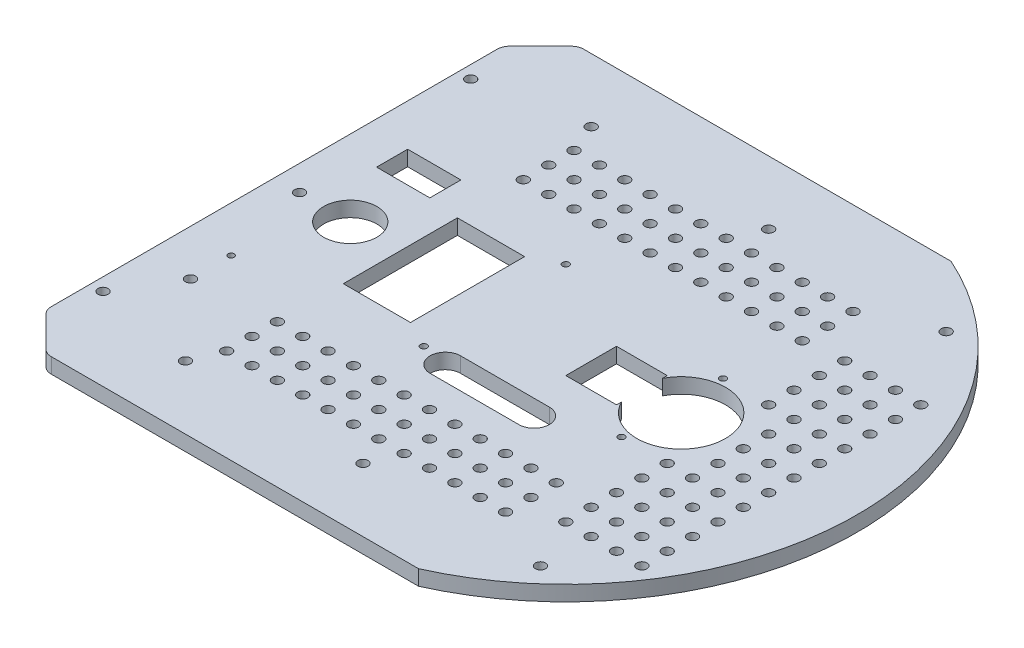
SolidWorks part; units mm, degrees
ref_plane "Front Plane" through (0, 0, 0) normal (0, 0, 1) x (1, 0, 0)
ref_plane "Top Plane" through (0, 0, 0) normal (0, 1, 0) x (1, 0, 0)
ref_plane "Right Plane" through (0, 0, 0) normal (1, 0, 0) x (0, 0, -1)
sketch "Sketch1" plane through (0, 0, 0) normal (0, 1, 0) x (1, 0, 0)
  line L0 (0, 80) -> (0, -80) construction
  line L1 (-46.9042, -105) -> (46.9042, -105)
  line L2 (-46.9042, 105) -> (46.9042, 105)
  line L7 (-70, 0) -> (70, 0) construction
  line L8 (-70, 80) -> (70, 80) construction
  line L9 (-70, 80) -> (-70, -80) construction
  line L10 (-70, -80) -> (70, -80) construction
  line L11 (70, 80) -> (70, -80) construction
  circle A0 centre (-70, 80) radius 2
  circle A1 centre (70, 80) radius 2
  circle A2 centre (70, -80) radius 2
  circle A3 centre (-70, -80) radius 2
  circle A4 centre (0, 80) radius 2
  circle A5 centre (70, 0) radius 2
  circle A6 centre (0, -80) radius 2
  arc A8 (-46.9042, 105) -> (-46.9042, -105) centre (0, 0) ccw
  arc A9 (46.9042, -105) -> (46.9042, 105) centre (0, 0) ccw
  point P0 (0, 0)
  point P13 (0, 0)
  dimension "D1" = 105
  dimension "D8" = 230
  dimension "D5" = 4
  dimension "D2" = 140
  dimension "D3" = 160
  dimension "D4" = 105
extrude "Boss-Extrude1" add sketch "Sketch1" along normal blind 6
sketch "Sketch2" plane through (0, 6, 0) normal (0, 1, 0) x (1, 0, 0)
  line L0 (0, 105) -> (0, -105) construction
  line L1 (46.9042, 105) -> (-46.9042, 105) construction
  line L2 (-46.9042, -105) -> (46.9042, -105) construction
  line L3 (-115, 0) -> (115, 0) construction
  line L4 (-17.5, -30) -> (17.5, -30) construction
  line L5 (-65.25, -22.5) -> (-38.75, -22.5)
  line L6 (-65.25, -22.5) -> (-65.25, 22.5)
  line L7 (-65.25, 22.5) -> (-38.75, 22.5)
  line L8 (-38.75, -22.5) -> (-38.75, 22.5)
  line L9 (-65.25, -22.5) -> (-38.75, 22.5) construction
  line L10 (-65.25, 22.5) -> (-38.75, -22.5) construction
  line L11 (-17.5, -24) -> (17.5, -24)
  line L12 (-17.5, -36) -> (17.5, -36)
  arc A0 (-46.9042, 105) -> (-46.9042, -105) centre (0, 0) ccw construction
  arc A1 (46.9042, -105) -> (46.9042, 105) centre (0, 0) ccw construction
  circle A2 centre (0, 0) radius 35 construction
  circle A3 centre (-28, 28) radius 1.3
  circle A4 centre (-28, -28) radius 1.3
  circle A5 centre (42, 20) radius 1.3
  circle A6 centre (42, -20) radius 1.3
  circle A7 centre (-85, 0) radius 10.5
  circle A8 centre (-97, -35) radius 1.2
  circle A10 centre (-97, -51) radius 2
  circle A12 centre (-105, 0) radius 2
  circle A13 centre (60, 50) radius 2
  circle A14 centre (70, 50) radius 2
  circle A15 centre (80, 50) radius 2
  circle A16 centre (90, 50) radius 2
  circle A17 centre (70, 40) radius 2
  circle A18 centre (80, 40) radius 2
  circle A19 centre (90, 40) radius 2
  circle A20 centre (70, 30) radius 2
  circle A21 centre (80, 30) radius 2
  circle A22 centre (90, 30) radius 2
  circle A23 centre (70, 20) radius 2
  circle A24 centre (80, 20) radius 2
  circle A25 centre (90, 20) radius 2
  circle A26 centre (70, 10) radius 2
  circle A27 centre (80, 10) radius 2
  circle A28 centre (90, 10) radius 2
  circle A29 centre (70, 0) radius 2
  circle A30 centre (80, 0) radius 2
  circle A31 centre (90, 0) radius 2
  circle A32 centre (70, -10) radius 2
  circle A33 centre (80, -10) radius 2
  circle A34 centre (90, -10) radius 2
  circle A35 centre (70, -20) radius 2
  circle A36 centre (80, -20) radius 2
  circle A37 centre (90, -20) radius 2
  circle A38 centre (70, -30) radius 2
  circle A39 centre (80, -30) radius 2
  circle A40 centre (90, -30) radius 2
  circle A41 centre (70, -40) radius 2
  circle A42 centre (80, -40) radius 2
  circle A43 centre (90, -40) radius 2
  circle A44 centre (70, -50) radius 2
  circle A45 centre (80, -50) radius 2
  circle A46 centre (90, -50) radius 2
  circle A47 centre (70, -60) radius 2
  circle A48 centre (80, -60) radius 2
  circle A49 centre (90, -60) radius 2
  circle A50 centre (60, 40) radius 2
  circle A51 centre (60, 30) radius 2
  circle A52 centre (60, 20) radius 2
  circle A56 centre (60, -20) radius 2
  circle A57 centre (60, -30) radius 2
  circle A58 centre (60, -40) radius 2
  circle A59 centre (60, -50) radius 2
  circle A60 centre (60, -60) radius 2
  arc A61 (-17.5, -24) -> (-17.5, -36) centre (-17.5, -30) ccw
  arc A62 (17.5, -36) -> (17.5, -24) centre (17.5, -30) ccw
  circle A63 centre (-65.25, -68.5) radius 2
  circle A64 centre (34.75, 48.5) radius 2
  circle A65 centre (-55.25, -68.5) radius 2
  circle A66 centre (-45.25, -68.5) radius 2
  circle A67 centre (-35.25, -68.5) radius 2
  circle A68 centre (-25.25, -68.5) radius 2
  circle A69 centre (-15.25, -68.5) radius 2
  circle A70 centre (-5.25, -68.5) radius 2
  circle A71 centre (4.75, -68.5) radius 2
  circle A72 centre (14.75, -68.5) radius 2
  circle A73 centre (24.75, -68.5) radius 2
  circle A74 centre (34.75, -68.5) radius 2
  circle A75 centre (44.75, -68.5) radius 2
  circle A76 centre (-55.25, -58.5) radius 2
  circle A77 centre (-45.25, -58.5) radius 2
  circle A78 centre (-35.25, -58.5) radius 2
  circle A79 centre (-25.25, -58.5) radius 2
  circle A80 centre (-15.25, -58.5) radius 2
  circle A81 centre (-5.25, -58.5) radius 2
  circle A82 centre (4.75, -58.5) radius 2
  circle A83 centre (14.75, -58.5) radius 2
  circle A84 centre (24.75, -58.5) radius 2
  circle A85 centre (34.75, -58.5) radius 2
  circle A86 centre (44.75, -58.5) radius 2
  circle A87 centre (-55.25, -48.5) radius 2
  circle A88 centre (-45.25, -48.5) radius 2
  circle A89 centre (-35.25, -48.5) radius 2
  circle A90 centre (-25.25, -48.5) radius 2
  circle A91 centre (-15.25, -48.5) radius 2
  circle A92 centre (-5.25, -48.5) radius 2
  circle A93 centre (4.75, -48.5) radius 2
  circle A94 centre (14.75, -48.5) radius 2
  circle A95 centre (24.75, -48.5) radius 2
  circle A96 centre (34.75, -48.5) radius 2
  circle A97 centre (44.75, -48.5) radius 2
  circle A98 centre (-65.25, -58.5) radius 2
  circle A99 centre (-65.25, -48.5) radius 2
  circle A100 centre (44.75, 48.5) radius 2
  circle A101 centre (44.75, 58.5) radius 2
  circle A102 centre (34.75, 58.5) radius 2
  circle A103 centre (34.75, 68.5) radius 2
  circle A104 centre (44.75, 68.5) radius 2
  circle A105 centre (24.75, 48.5) radius 2
  circle A106 centre (24.75, 58.5) radius 2
  circle A107 centre (24.75, 68.5) radius 2
  circle A108 centre (14.75, 68.5) radius 2
  circle A109 centre (14.75, 58.5) radius 2
  circle A110 centre (14.75, 48.5) radius 2
  circle A111 centre (4.75, 48.5) radius 2
  circle A112 centre (4.75, 58.5) radius 2
  circle A113 centre (4.75, 68.5) radius 2
  circle A114 centre (-5.25, 68.5) radius 2
  circle A115 centre (-5.25, 58.5) radius 2
  circle A116 centre (-5.25, 48.5) radius 2
  circle A117 centre (-15.25, 48.5) radius 2
  circle A118 centre (-15.25, 58.5) radius 2
  circle A119 centre (-15.25, 68.5) radius 2
  circle A120 centre (-25.25, 68.5) radius 2
  circle A121 centre (-25.25, 58.5) radius 2
  circle A122 centre (-25.25, 48.5) radius 2
  circle A123 centre (-35.25, 48.5) radius 2
  circle A124 centre (-35.25, 68.5) radius 2
  circle A125 centre (-35.25, 58.5) radius 2
  circle A126 centre (-45.25, 68.5) radius 2
  circle A127 centre (-45.25, 58.5) radius 2
  circle A128 centre (-45.25, 48.5) radius 2
  circle A129 centre (-55.25, 48.5) radius 2
  circle A130 centre (-55.25, 58.5) radius 2
  circle A131 centre (-55.25, 68.5) radius 2
  circle A132 centre (-65.25, 68.5) radius 2
  circle A133 centre (-65.25, 48.5) radius 2
  circle A134 centre (-65.25, 58.5) radius 2
  circle A135 centre (45.5, 0) radius 17.5
  circle A136 centre (60, 0) radius 2 [skipped]
  circle A137 centre (60, 10) radius 2 [skipped]
  circle A138 centre (60, -10) radius 2 [skipped]
  point P28 (-52, 0)
  point P46 (0, -30)
  dimension "D1" = 70
  dimension "D2" = 2.6
  dimension "D9" = 21
  dimension "D14" = 2.4
  dimension "D20" = 4
  dimension "D21" = 4
  dimension "D24" = 4
  dimension "D29" = 6
  dimension "D31" = 35
  dimension "D32" = 4
  dimension "D3" = 28
  dimension "D4" = 42
  dimension "D5" = 40
  dimension "D6" = 56
  dimension "D7" = 28
  dimension "D8" = 20
  dimension "D10" = 85
  dimension "D11" = 26.5
  dimension "D12" = 45
  dimension "D13" = 52
  dimension "D16" = 35
  dimension "D17" = 18
  dimension "D18" = 16
  dimension "D22" = 10
  dimension "D23" = 50
  dimension "D25" = 60
  dimension "D28" = 35
  dimension "D30" = 30
  dimension "D33" = 46
  dimension "D34" = 45.5
  dimension "D26" = 4
  dimension "D27" = 12
  dimension "D35" = 12
  dimension "D36" = 3
extrude "Cut-Extrude1" cut sketch "Sketch2" against normal blind 10
ref_plane "Plane1" through (0, 6, 0) normal (0, 1, 0) x (1, 0, 0)
sketch "Sketch3" plane through (0, 6, 0) normal (0, 1, 0) x (1, 0, 0)
  line L0 (-46.9042, 105) -> (-115, 105)
  line L1 (-46.9042, -105) -> (-115, -105)
  line L2 (-115, -105) -> (-115, 105)
  arc A1 (-46.9042, 105) -> (-46.9042, -105) centre (0, 0) ccw construction
  arc A2 (-46.9042, 105) -> (-46.9042, -105) centre (0, 0) ccw
  dimension "D1" = 68.0958
extrude "Boss-Extrude2" add sketch "Sketch3" against normal blind 6 contours A2 L0 L2 | A2 L2 L1 region at (-96.2941, 6, -80.5417) region at (-96.2941, 6, 80.5417)
chamfer "Chamfer1" distance 15 angle 45 2 edges at (-115, 3, -105) (-115, 3, 105)
fillet "Fillet1" radius 5 4 edges at (-100, 3, 105) (-115, 3, 90) (-115, 3, -90) (-100, 3, -105)
sketch "Sketch4" plane through (0, 6, 0) normal (0, 1, 0) x (1, 0, 0)
  line L0 (-115, 0) -> (110.0849, 0) construction
  line L1 (-115, -87.9289) -> (-115, 87.9289) construction
  circle A0 centre (-110, 72.5) radius 2
  circle A1 centre (-110, -72.5) radius 2
  dimension "D1" = 4
  dimension "D2" = 4
  dimension "D3" = 5
  dimension "D4" = 72.5
  dimension "D5" = 72.5
extrude "Cut-Extrude2" cut sketch "Sketch4" against normal blind 10
sketch "Sketch5" plane through (0, 6, 0) normal (0, 1, 0) x (1, 0, 0)
  line L0 (-115, -87.9289) -> (-115, 87.9289) construction
  line L1 (-98.5, 36.125) -> (-77.5, 36.125)
  line L2 (-98.5, 36.125) -> (-98.5, 23.875)
  line L3 (-98.5, 23.875) -> (-77.5, 23.875)
  line L4 (-77.5, 36.125) -> (-77.5, 23.875)
  line L5 (-98.5, 36.125) -> (-77.5, 23.875) construction
  line L6 (-98.5, 23.875) -> (-77.5, 36.125) construction
  line L7 (46.9042, 105) -> (-97.9289, 105) construction
  point P0 (-88, 30)
  dimension "D1" = 12.25
  dimension "D2" = 21
  dimension "D3" = 27
  dimension "D4" = 75
extrude "Cut-Extrude3" cut sketch "Sketch5" against normal blind 10
sketch "Sketch6" plane through (0, 6, 0) normal (0, 1, 0) x (1, 0, 0)
  line L0 (46.9042, 105) -> (-97.9289, 105) construction
  line L1 (30, 10) -> (10, 10)
  line L2 (30, 10) -> (30, -10)
  line L3 (30, -10) -> (10, -10)
  line L4 (10, 10) -> (10, -10)
  line L5 (30, 10) -> (10, -10) construction
  line L6 (30, -10) -> (10, 10) construction
  point P0 (20, 0)
  dimension "D1" = 20
  dimension "D2" = 20
  dimension "D3" = 20
  dimension "D4" = 105
extrude "Cut-Extrude4" cut sketch "Sketch6" against normal blind 10
